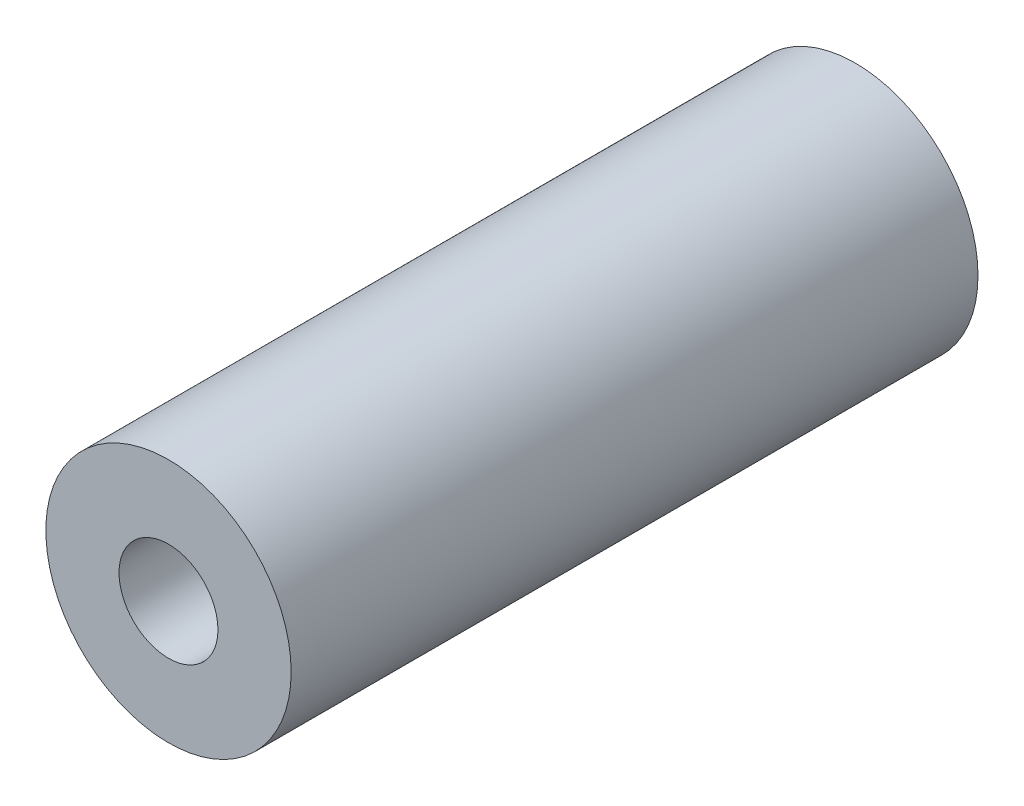
SolidWorks part; units mm, degrees
ref_plane "Front Plane" through (0, 0, 0) normal (0, 0, 1) x (1, 0, 0)
ref_plane "Top Plane" through (0, 0, 0) normal (0, 1, 0) x (1, 0, 0)
ref_plane "Right Plane" through (0, 0, 0) normal (1, 0, 0) x (0, 0, -1)
sketch "Sketch1" plane through (0, 0, 0) normal (0, 0, 1) x (1, 0, 0)
  circle A0 centre (0, 0) radius 7.9375
  circle A1 centre (0, 0) radius 3.2004
  dimension "OD" = 15.875
  dimension "ID" = 6.4008
extrude "Extrude1" add sketch "Sketch1" along normal mid plane 44.45
